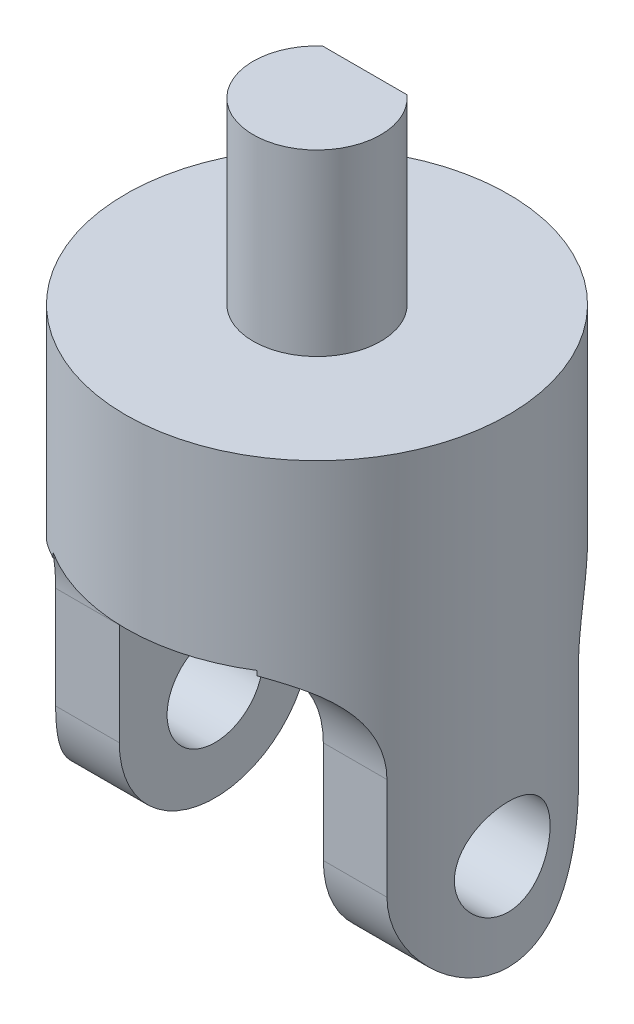
SolidWorks part; units mm, degrees
ref_plane "Ön Düzlem" through (0, 0, 0) normal (0, 0, 1) x (1, 0, 0)
ref_plane "Üst Düzlem" through (0, 0, 0) normal (0, 1, 0) x (1, 0, 0)
ref_plane "Sağ Düzlem" through (0, 0, 0) normal (1, 0, 0) x (0, 0, -1)
sketch "Çizim2" plane through (0, 0, 0) normal (0, 1, 0) x (1, 0, 0)
  circle A0 centre (0, 0) radius 19.05
  dimension "D1" = 38.1
extrude "Yükseklik-Ekstrüzyon2" add sketch "Çizim2" against normal blind 18.42
ref_plane "Düzlem1" through (10.16, 0, 0) normal (1, 0, 0) x (0, 0, -1)
sketch "Çizim3" plane through (10.16, 0, 0) normal (1, 0, 0) x (0, 0, -1)
  line L0 (-9.53, -38.1) -> (-9.53, -18.42)
  line L1 (-19.05, -18.42) -> (19.05, -18.42) construction
  line L2 (-9.53, -18.42) -> (9.53, -18.42)
  line L3 (9.53, -18.42) -> (9.53, -38.1)
  circle A0 centre (0, -38.1) radius 4.765
  arc A1 (-9.53, -38.1) -> (9.53, -38.1) centre (0, -38.1) ccw
  dimension "D1" = 9.53
  dimension "D2" = 19.06
  dimension "D3" = 19.68
extrude "Yükseklik-Ekstrüzyon4" add sketch "Çizim3" along normal up to surface (8.2844 mm away) up to face at (0, -18.42, 19.05)
mirror "Aynalama3" about plane through (0, 0, 0) normal (1, 0, 0) of "Yükseklik-Ekstrüzyon4"
fillet "Radyus1" radius 9.53 4 edges at (13.3274, -18.42, 9.53) (-13.3274, -18.42, 9.53) (-13.3274, -18.42, -9.53) (13.3274, -18.42, -9.53)
sketch "Çizim5" plane through (0, 0, 0) normal (0, 1, 0) x (1, 0, 0)
  circle A0 centre (0, 0) radius 6.35
  dimension "D1" = 12.7
extrude "Yükseklik-Ekstrüzyon5" add sketch "Çizim5" along normal blind 17.81
sketch "Çizim6" plane through (0, 0, 0) normal (1, 0, 0) x (0, 0, -1)
  line L1 (6.35, 17.81) -> (4.76, 17.81)
  line L2 (6.35, 17.81) -> (6.35, 6.38)
  line L3 (6.35, 6.38) -> (4.76, 6.38)
  line L4 (4.76, 17.81) -> (4.76, 6.38)
  dimension "D1" = 11.43
  dimension "D2" = 1.59
extrude "Kes-Ekstrüzyon2" cut sketch "Çizim6" against normal mid plane 17.81
